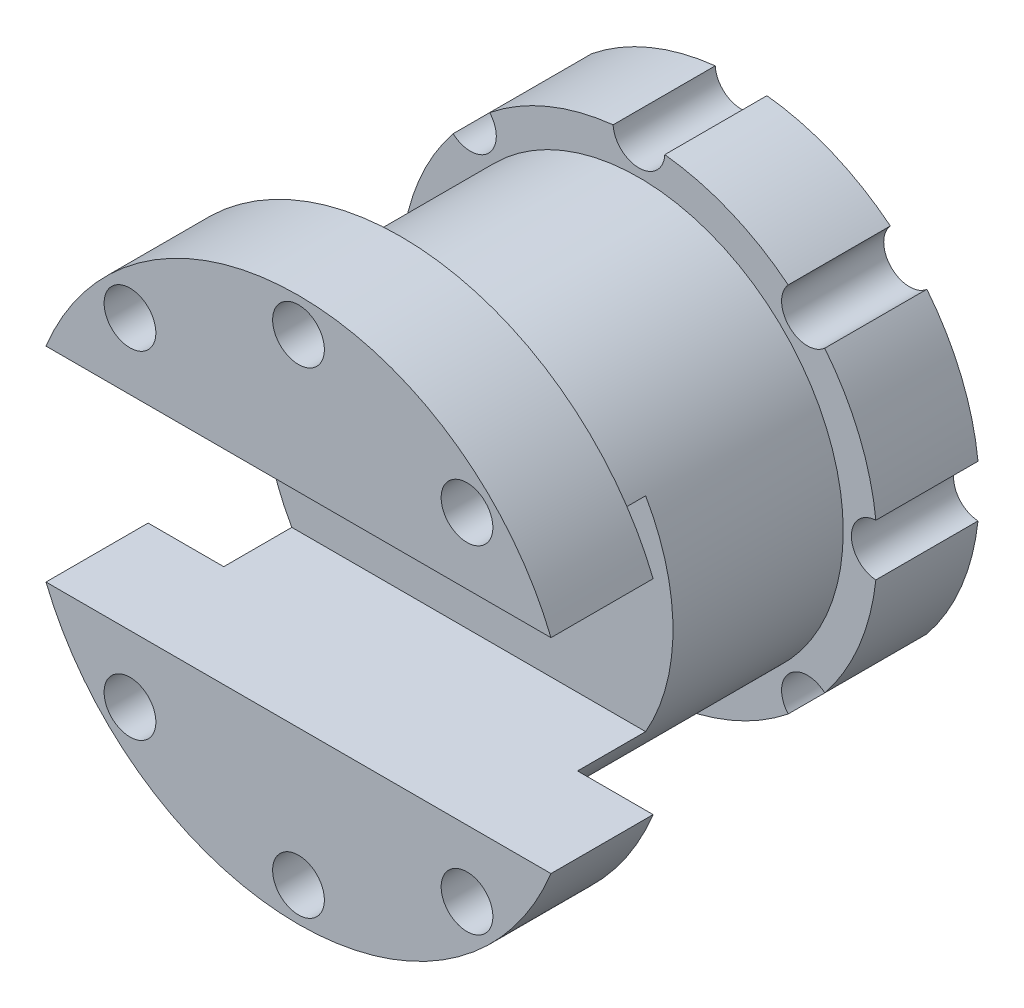
SolidWorks part; units mm, degrees
ref_plane "Front Plane" through (0, 0, 0) normal (0, 0, 1) x (1, 0, 0)
ref_plane "Top Plane" through (0, 0, 0) normal (0, 1, 0) x (1, 0, 0)
ref_plane "Right Plane" through (0, 0, 0) normal (1, 0, 0) x (0, 0, -1)
sketch "Sketch1" plane through (0, 0, 0) normal (0, 0, 1) x (1, 0, 0)
  circle A0 centre (0, 0) radius 12.7
  circle A1 centre (0, 0) radius 44.45
  circle A2 centre (0, 0) radius 38.1
  circle A3 centre (0, 44.45) radius 4.826
  circle A4 centre (31.4309, 31.4309) radius 4.826
  circle A5 centre (44.45, 0) radius 4.826
  circle A6 centre (31.4309, -31.4309) radius 4.826
  circle A7 centre (0, -44.45) radius 4.826
  circle A8 centre (-31.4309, -31.4309) radius 4.826
  circle A9 centre (-44.45, 0) radius 4.826
  circle A10 centre (-31.4309, 31.4309) radius 4.826
  point P23 (0, 0)
  dimension "D1" = 25.4
  dimension "D2" = 88.9
  dimension "D3" = 76.2
  dimension "D4" = 9.652
  dimension "D5" = 8
extrude "Boss-Extrude1" add sketch "Sketch1" along normal blind 63.5 contours A2 A0 region at (-37.0224, 0, 0)
extrude "Boss-Extrude2" add sketch "Sketch1<3>" along normal blind 19.05 contours A1 A2 region at (38.3742, 0, 0)
sketch "Sketch1<3>" plane through (0, 0, 0) normal (0, 0, 1) x (1, 0, 0) same geometry as "Sketch1"
sketch "Sketch2" plane through (0, 0, 63.5) normal (0, 0, 1) x (1, 0, 0)
  line L0 (-47.0929, 19.05) -> (47.0929, 19.05)
  line L1 (-47.0929, -19.05) -> (47.0929, -19.05)
  line L2 (-63.2203, 0) -> (63.2203, 0) construction
  line L3 (-47.0929, 19.05) -> (-47.0929, -19.05)
  line L4 (47.0929, 19.05) -> (47.0929, -19.05)
  arc A0 (-47.0929, -19.05) -> (47.0929, -19.05) centre (0, 0) ccw
  circle A1 centre (0, 44.45) radius 4.826
  circle A2 centre (0, 0) radius 44.45 construction
  arc A3 (47.0929, 19.05) -> (-47.0929, 19.05) centre (0, 0) ccw
  circle A4 centre (31.4309, 31.4309) radius 4.826
  circle A6 centre (31.4309, -31.4309) radius 4.826
  circle A7 centre (0, -44.45) radius 4.826
  circle A8 centre (-31.4309, -31.4309) radius 4.826
  circle A10 centre (-31.4309, 31.4309) radius 4.826
  circle A11 centre (44.45, 0) radius 4.826 [skipped]
  circle A12 centre (-44.45, 0) radius 4.826 [skipped]
  point P14 (0, 0)
  point P30 (0, 0)
  circle M6 centre (0, 0) radius 12.7
  circle M7 centre (0, 0) radius 38.1
  dimension "D1" = 101.6
  dimension "D2" = 9.652
  dimension "D3" = 38.1
  dimension "D4" = 8
extrude "Boss-Extrude3" add sketch "Sketch2" along normal blind 19.05 contours L0 A3 A10 A4 A1 M7 | L0 M7 | L1 A0 A8 A7 A6 M7 | L1 M7 region at (0, 49.8061, 63.5) region at (0, 26.8613, 63.5) region at (0, -39.0939, 63.5) region at (0, -26.8613, 63.5)
extrude "Cut-Extrude1" cut sketch "Sketch2<3>" against normal blind 12.7 contours L2 L0 M7 M6 | L2 L1 M7 M6 region at (0, 18.2645, 63.5) region at (-25.4, -0.7855, 63.5)
sketch "Sketch2<3>" plane through (0, 0, 63.5) normal (0, 0, 1) x (1, 0, 0) same geometry as "Sketch2"
